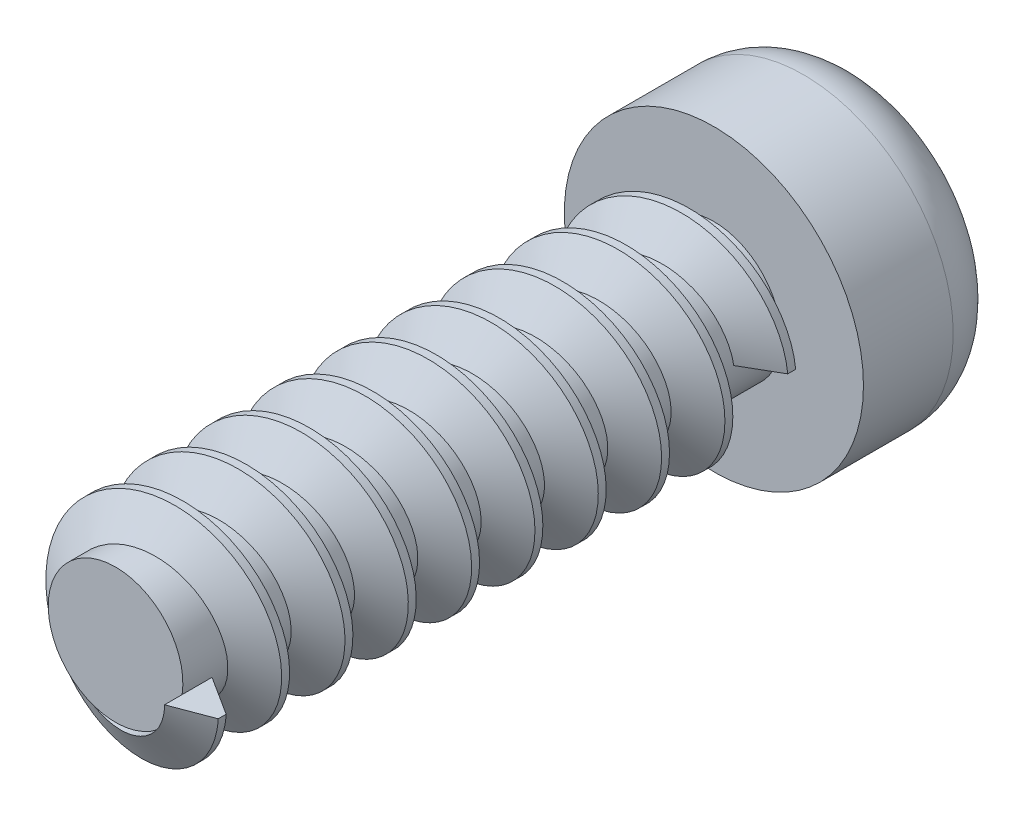
SolidWorks part; units mm, degrees
ref_plane "Front Plane" through (0, 0, 0) normal (0, 0, 1) x (1, 0, 0)
ref_plane "Top Plane" through (0, 0, 0) normal (0, 1, 0) x (1, 0, 0)
ref_plane "Right Plane" through (0, 0, 0) normal (1, 0, 0) x (0, 0, -1)
sketch "Sketch1" plane through (0, 0, 0) normal (0, 0, 1) x (1, 0, 0)
  circle A0 centre (0, 0) radius 5
  dimension "D1" = 10
extrude "Boss-Extrude1" add sketch "Sketch1" along normal blind 5
sketch "Sketch2" plane through (0, 0, 5) normal (0, 0, 1) x (1, 0, 0)
  circle A0 centre (0, 0) radius 2.25
  dimension "D1" = 4.5
extrude "Boss-Extrude2" add sketch "Sketch2" along normal blind 20
thread "Thread1" pitch 2.1167 method extrude profile "Thread Profile1" start angle 0, offset 0, length 19, pitch 2.1167, diameter 4.5
ref_plane "Plane1" through (2.25, 0, 5) normal (0, -1, 0) x (1, 0, 0)
sketch "Thread Profile1" plane through (2.25, 0, 5) normal (0, -1, 0) x (1, 0, 0)
  line L0 (0, 0) -> (0, 2.1167) construction
  line L1 (0, 0) -> (1.1457, 0.6615)
  line L2 (1.1457, 0.6615) -> (1.1457, 0.926)
  line L3 (1.1457, 0.926) -> (0, 1.5875)
  line L4 (1.1457, 0.7937) -> (0, 0.7937) construction
  line L11 (0, 0) -> (0, 1.5875)
  point P2 (0, 0)
  dimension "Pitch" = 2.1167
  dimension "Profile_Angle" = 60
  dimension "Profile_Land" = 0.2646
  dimension "Profile_Height" = 1.1457
fillet "Fillet1" radius 2 1 edges at (5, 0, 0)
